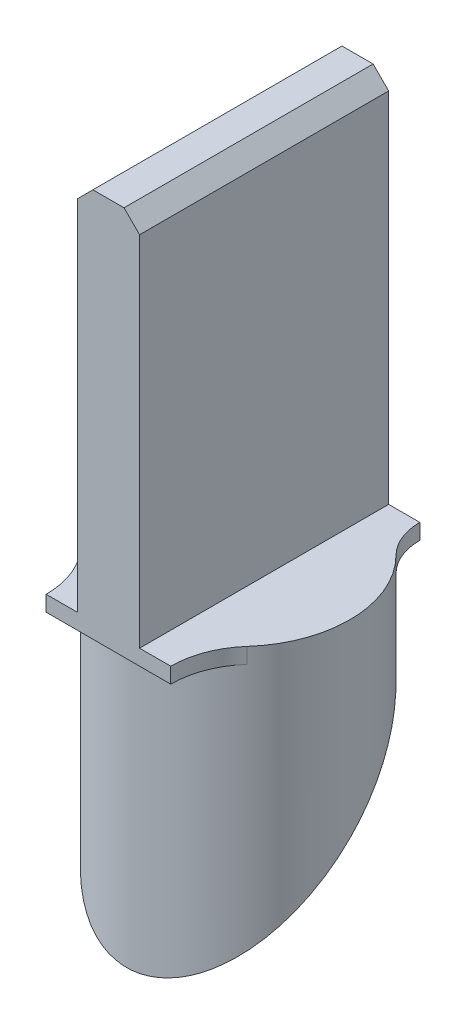
SolidWorks part; units mm, degrees
ref_plane "Front Plane" through (0, 0, 0) normal (0, 0, 1) x (1, 0, 0)
ref_plane "Top Plane" through (0, 0, 0) normal (0, 1, 0) x (1, 0, 0)
ref_plane "Right Plane" through (0, 0, 0) normal (1, 0, 0) x (0, 0, -1)
sketch "Sketch2" plane through (0, 0, 0) normal (1, 0, 0) x (0, 0, -1)
  line L0 (1.0414, 1052.7211) -> (1.0414, 994.4816) construction
  line L1 (1.0414, 1052.7211) -> (-21.7283, 1052.7211)
  line L2 (-21.7283, 1052.7211) -> (-21.7283, 994.4816)
  line L3 (-21.7283, 994.4816) -> (1.0414, 994.4816)
  line L4 (1.0414, 1052.7211) -> (1.0414, 994.4816)
revolve "Revolve1" add sketch "Sketch2" angle 360 about L0
sketch "Sketch3" plane through (0, 0, 0) normal (1, 0, 0) x (0, 0, -1)
  line L0 (-21.7283, 994.4816) -> (23.8111, 1040.0211)
  line L1 (23.8111, 1040.0211) -> (23.8111, 994.4816)
  line L2 (23.8111, 994.4816) -> (-21.7283, 994.4816)
extrude "Cut-Extrude1" cut sketch "Sketch3" against normal through all both and the other way through all
shell "Shell1" thickness 3.175 removed face at (0, 1040.0211, -23.8111)
sketch "Sketch4" plane through (0, 1052.7211, 0) normal (0, 1, 0) x (1, 0, 0)
  line L12 (12.7, -25.4) -> (12.7, 25.4) construction
  line L13 (12.7, -25.4) -> (-12.7, -25.4)
  line L14 (-12.7, -25.4) -> (-12.7, 25.4) construction
  line L15 (12.7, 25.4) -> (-12.7, 25.4)
  line L16 (12.7, -25.4) -> (-12.7, 25.4) construction
  line L17 (-12.7, -25.4) -> (12.7, 25.4) construction
  arc A0 (12.7, 25.4) -> (16.1231, 17.1195) centre (24.4267, 25.4) ccw
  circle A1 centre (0, 1.0414) radius 22.7697
  arc A2 (-16.1231, 17.1195) -> (-17.0016, -14.1048) centre (0, 1.0414) ccw
  arc A3 (17.0016, -14.1048) -> (12.7, -25.4) centre (29.6804, -25.4) ccw
  arc A4 (-12.7, -25.4) -> (-17.0016, -14.1048) centre (-29.6804, -25.4) ccw
  arc A5 (-12.7, 25.4) -> (-16.1231, 17.1195) centre (-24.4267, 25.4) cw
  arc A6 (17.0016, -14.1048) -> (16.1231, 17.1195) centre (0, 1.0414) ccw
  point P0 (0, 0)
  point P9 (21.4584, -8.525)
  point P11 (13.0289, -25.7839)
  dimension "D1" = 25.4
  dimension "D2" = 50.8
  dimension "D3" = 0
extrude "Boss-Extrude1" add sketch "Sketch4" along normal blind 3.175
sketch "Sketch5" plane through (0, 1055.8961, 0) normal (0, 1, 0) x (1, 0, 0)
  line L1 (6.35, -25.4) -> (6.35, 25.4)
  line L2 (6.35, -25.4) -> (-6.35, -25.4)
  line L3 (-6.35, -25.4) -> (-6.35, 25.4)
  line L4 (6.35, 25.4) -> (-6.35, 25.4)
  line L5 (-6.35, 0) -> (6.35, 0) construction
  line L6 (0, -25.4) -> (0, 25.4) construction
  line L7 (12.7, 25.4) -> (-12.7, 25.4) construction
  point P0 (0, 0)
  point P4 (25.4, -6.35)
  point P5 (0, 25.4)
  point P7 (-25.4, 6.35)
  point P9 (14.6654, 0)
  dimension "D1" = 12.7
extrude "Boss-Extrude2" add sketch "Sketch5" along normal blind 76.2
chamfer "Chamfer1" distance 3.175 angle 45 2 edges at (6.35, 1132.0961, 0) (-6.35, 1132.0961, 0)
sketch "Sketch6" plane through (0, 1132.0961, 0) normal (0, 1, 0) x (1, 0, 0)
  line L0 (0, -22.225) -> (0, 22.225) construction
  point P0 (0, 22.225)
  point P4 (0, 0)
  dimension "D1" = 44.45
sketch "Sketch7" plane through (0, 1052.7211, 0) normal (0, -1, 0) x (1, 0, 0)
  line L0 (0, 22.225) -> (0, -22.225) construction
  line L1 (0, 22.225) -> (0, -22.225) construction
